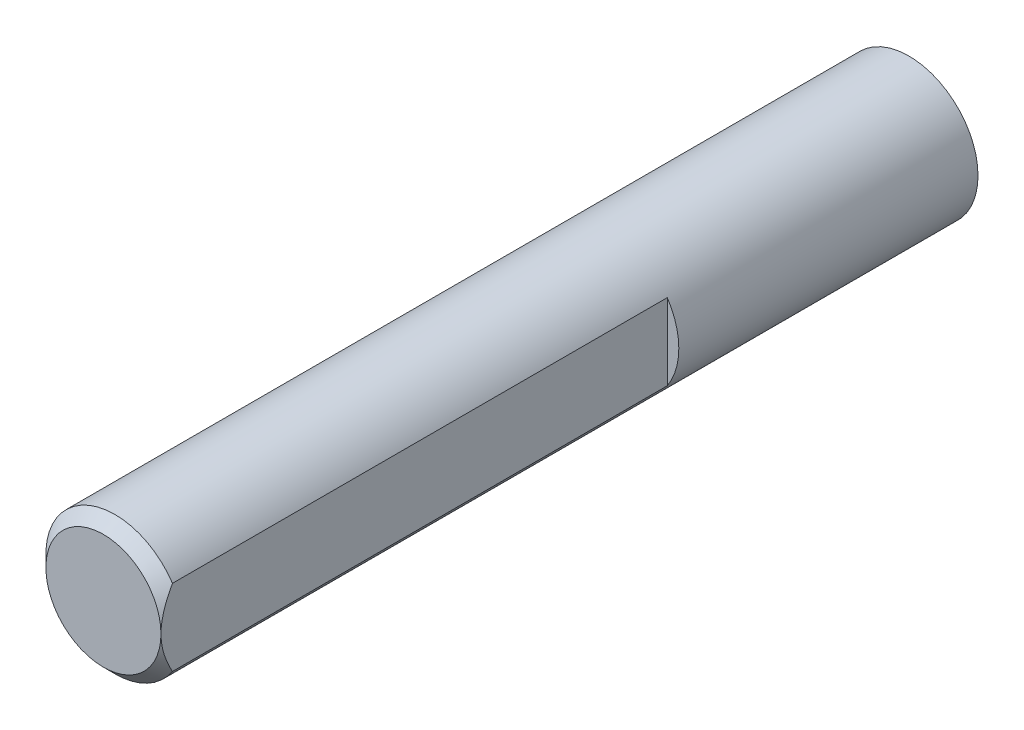
SolidWorks part; units mm, degrees
material "AISI 1020"
ref_plane "Front Plane" through (0, 0, 0) normal (0, 0, 1) x (1, 0, 0)
ref_plane "Top Plane" through (0, 0, 0) normal (0, 1, 0) x (1, 0, 0)
ref_plane "Right Plane" through (0, 0, 0) normal (1, 0, 0) x (0, 0, -1)
sketch "Sketch1" plane through (0, 0, 0) normal (0, 0, 1) x (1, 0, 0)
  circle A0 centre (0, 0) radius 3
  dimension "D1" = 6
extrude "Boss-Extrude1" add sketch "Sketch1" along normal blind 35
sketch "Sketch2" plane through (0, 0, 35) normal (0, 0, 1) x (1, 0, 0)
  line L0 (2.5, 1.6583) -> (2.5, -1.6583)
  line L1 (0, 0) -> (2.5, 0) construction
  line L2 (2.5, 0) -> (3, 0) construction
  circle A1 centre (0, 0) radius 3
  arc A2 (2.5, -1.6583) -> (2.5, 1.6583) centre (0, 0) ccw
  dimension "D2" = 0.5
  dimension "D1" = 0
extrude "Cut-Extrude1" cut sketch "Sketch2" against normal blind 22
chamfer "Chamfer1" distance 0.5 angle 45 1 edges at (-3, 0, 35)
